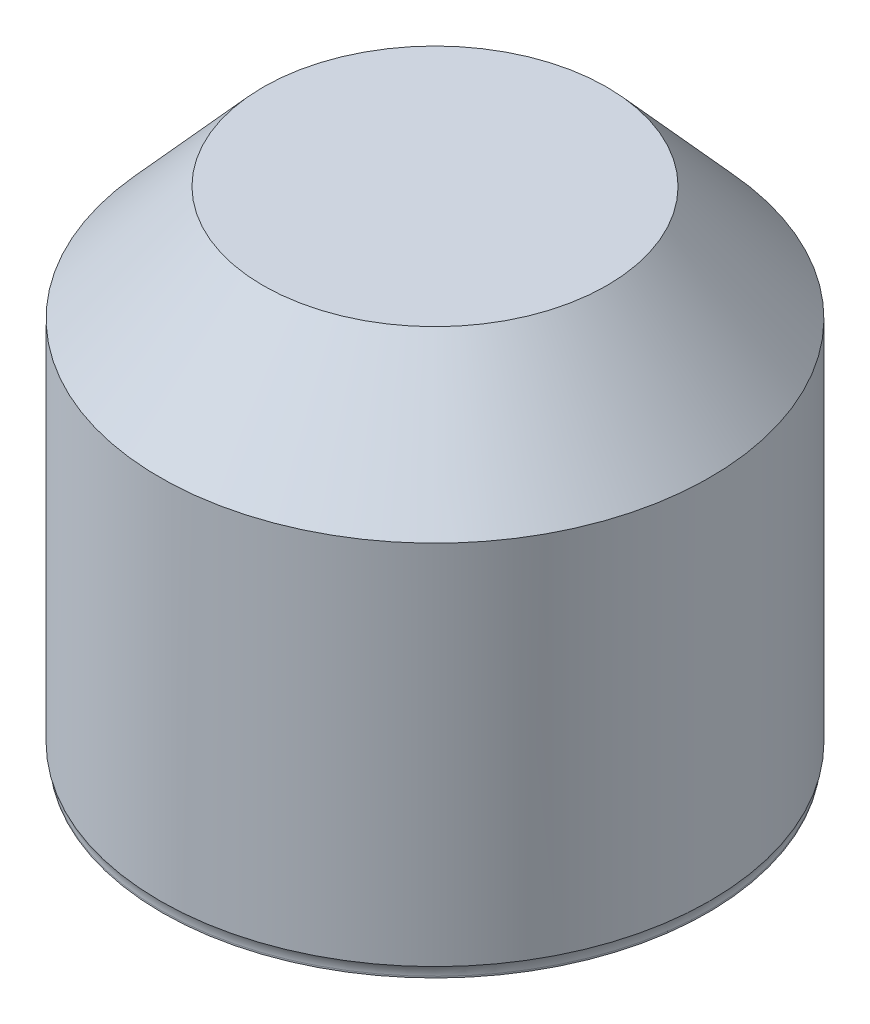
SolidWorks part; units mm, degrees
ref_plane "Front Plane" through (0, 0, 0) normal (0, 0, 1) x (1, 0, 0)
ref_plane "Top Plane" through (0, 0, 0) normal (0, 1, 0) x (1, 0, 0)
ref_plane "Right Plane" through (0, 0, 0) normal (1, 0, 0) x (0, 0, -1)
sketch "Sketch1" plane through (0, 0, 0) normal (0, 1, 0) x (1, 0, 0)
  circle A0 centre (0, 0) radius 59.5
  circle A2 centre (0, 0) radius 52
  dimension "D1" = 119
  dimension "D3" = 104
extrude "Boss-Extrude1" add sketch "Sketch1" along normal blind 2.5
sketch "Sketch2" plane through (0, 2.5, 0) normal (0, 1, 0) x (1, 0, 0)
  circle A0 centre (0, 0) radius 60
  circle A1 centre (0, 0) radius 46.365
  dimension "D1" = 120
  dimension "D2" = 92.73
extrude "Boss-Extrude2" add sketch "Sketch2" along normal blind 70
sketch "Sketch3" plane through (0, 72.5, 0) normal (0, 1, 0) x (1, 0, 0)
  circle A0 centre (0, 0) radius 60
extrude "Boss-Extrude3" add sketch "Sketch3" along normal blind 10
fillet "Fillet1" radius 1 1 edges at (0, 2.5, 46.365)
ref_plane "Plane1" through (0, 107.5, 0) normal (0, 1, 0) x (1, 0, 0)
sketch "Sketch4" plane through (0, 107.5, 0) normal (0, 1, 0) x (1, 0, 0)
  circle A0 centre (0, 0) radius 37.5
  dimension "D1" = 75
loft "Loft1" add profiles "Sketch4" section edge at (0, 82.5, 60) section "Sketch4" connector at (-60, 82.5, 0.0377) connector at (-37.4981, 107.5, 0.377)
fillet "Fillet2" radius 5 1 edges at (0, 72.5, 46.365)
fillet "Fillet3" radius 5 1 edges at (0, 2.5, 59.5)
sketch "Sketch6" plane through (0, 0, 0) normal (0, 0, 1) x (1, 0, 0)
  line L2 (-21.3414, 107.5) -> (-98.9235, 107.5) construction
  line L3 (55, 107.5) -> (-55, 107.5) construction
  line L4 (-37.5, 107.5) -> (-60, 82.5) construction
  dimension "D1" = 48.013
